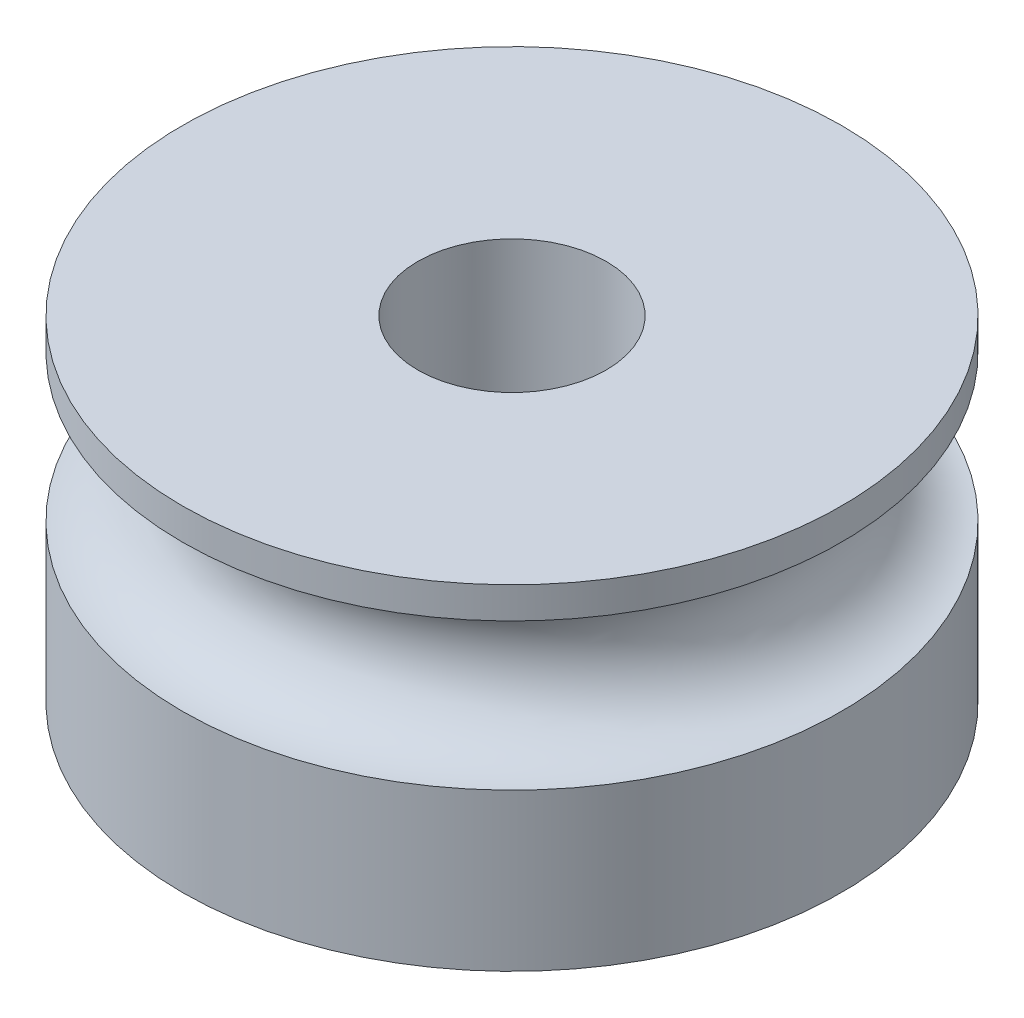
SolidWorks part; units mm, degrees
ref_plane "Front Plane" through (0, 0, 0) normal (0, 0, 1) x (1, 0, 0)
ref_plane "Top Plane" through (0, 0, 0) normal (0, 1, 0) x (1, 0, 0)
ref_plane "Right Plane" through (0, 0, 0) normal (1, 0, 0) x (0, 0, -1)
sketch "Sketch1" plane through (0, 0, 0) normal (0, 1, 0) x (1, 0, 0)
  circle A0 centre (0, 0) radius 7.875
  circle A1 centre (0, 0) radius 2.25
  dimension "D1" = 15.75
  dimension "D2" = 4.5
extrude "Boss-Extrude1" add sketch "Sketch1" along normal blind 8
sketch "Sketch2" plane through (0, 8, 0) normal (0, 1, 0) x (1, 0, 0)
  circle A0 centre (0, 0) radius 4
  circle A1 centre (0, 0) radius 2.25 construction
  dimension "D1" = 8
extrude "Cut-Extrude1" [suppressed] cut sketch "Sketch2" against normal blind 3 draft 45
sketch "Sketch3" plane through (0, 0, 0) normal (0, -1, 0) x (-1, 0, 0)
  circle A0 centre (0, 0) radius 4
  circle A1 centre (0, 0) radius 2.25 construction
  dimension "D1" = 8
extrude "Cut-Extrude2" cut sketch "Sketch3" against normal blind 3
sketch "Sketch4" plane through (0, 3, 0) normal (0, -1, 0) x (1, 0, 0)
  circle A0 centre (0, 0) radius 2.5
  circle A1 centre (0, 0) radius 4
  circle A2 centre (0, 0) radius 4 construction
  dimension "D1" = 5
extrude "Boss-Extrude2" [suppressed] add sketch "Sketch4" along normal blind 2
sketch "Sketch5" [suppressed] plane through (0, 8, 0) normal (0, 1, 0) x (1, 0, 0)
  line L0 (4.437, 6.506) -> (4.437, -6.506)
  line L1 (3.937, -6.9653) -> (3.937, 4.6059) construction
  circle A0 centre (0, 0) radius 7.875 construction
  arc A1 (4.437, -6.506) -> (4.437, 6.506) centre (0, 0) ccw
  dimension "D1" = 0.5
extrude "Boss-Extrude3" [suppressed] add sketch "Sketch5" along normal blind 8
sketch "Sketch6" [suppressed] plane through (3.937, 0, 0) normal (1, 0, 0) x (0, 0, -1)
  line L0 (14.052, 7.7042) -> (-6.463, 7.7042) construction
  line L1 (-6.506, 16) -> (-3.506, 16)
  line L2 (-6.506, 16) -> (-6.506, 7.7042)
  line L3 (-6.506, 7.7042) -> (-3.506, 7.7042)
  line L4 (-3.506, 16) -> (-3.506, 7.7042)
  line L5 (0, 16) -> (0, 7.7042) construction
  line L6 (6.506, 16) -> (-6.506, 16) construction
  line L7 (3.506, 16) -> (3.506, 7.7042)
  line L8 (6.506, 7.7042) -> (3.506, 7.7042)
  line L9 (6.506, 16) -> (6.506, 7.7042)
  line L10 (6.506, 16) -> (3.506, 16)
  dimension "D1" = 3
extrude "Cut-Extrude3" [suppressed] cut sketch "Sketch6" along normal through all
sketch "Sketch7" plane through (0, 8, 0) normal (0, 1, 0) x (1, 0, 0)
  circle A0 centre (0, 0) radius 1.25
  circle A1 centre (0, 0) radius 2.5
  dimension "D1" = 2.5
  dimension "D2" = 5
extrude "Boss-Extrude4" [suppressed] add sketch "Sketch7" along normal blind 10 separate body
sketch "Sketch9" plane through (11.2113, 0, 0) normal (1, 0, 0) x (0, 0, -1)
  circle A0 centre (-6.463, 18.7042) radius 6.35
  circle A1 centre (-6.463, 18.7042) radius 6.35 construction
extrude "Cut-Extrude4" [suppressed] cut sketch "Sketch9" against normal through all
sketch "Sketch10" plane through (6.1024, 0, 0) normal (1, 0, 0) x (0, 0, -1)
  circle A0 centre (8.6773, 18.7042) radius 8.5
  dimension "D1" = 17
extrude "Cut-Extrude5" [suppressed] cut sketch "Sketch10" against normal through all
ref_plane "Plane1" [suppressed] through (2.5, 0, 0) normal (1, 0, 0) x (0, 0, -1)
sketch "Sketch11" plane through (0, 0, 0) normal (0, 0, 1) x (1, 0, 0)
  line L0 (-7.875, 8) -> (-7.875, 0) construction
  line L1 (7.875, 8) -> (-7.875, 8) construction
  line L2 (0, 0) -> (0, 7.6573) construction
  circle A0 centre (-7.875, 5.5) radius 1.75
  dimension "D1" = 3.5
  dimension "D2" = 2.5
revolve "Cut-Revolve1" cut sketch "Sketch11" angle 360 about L2
